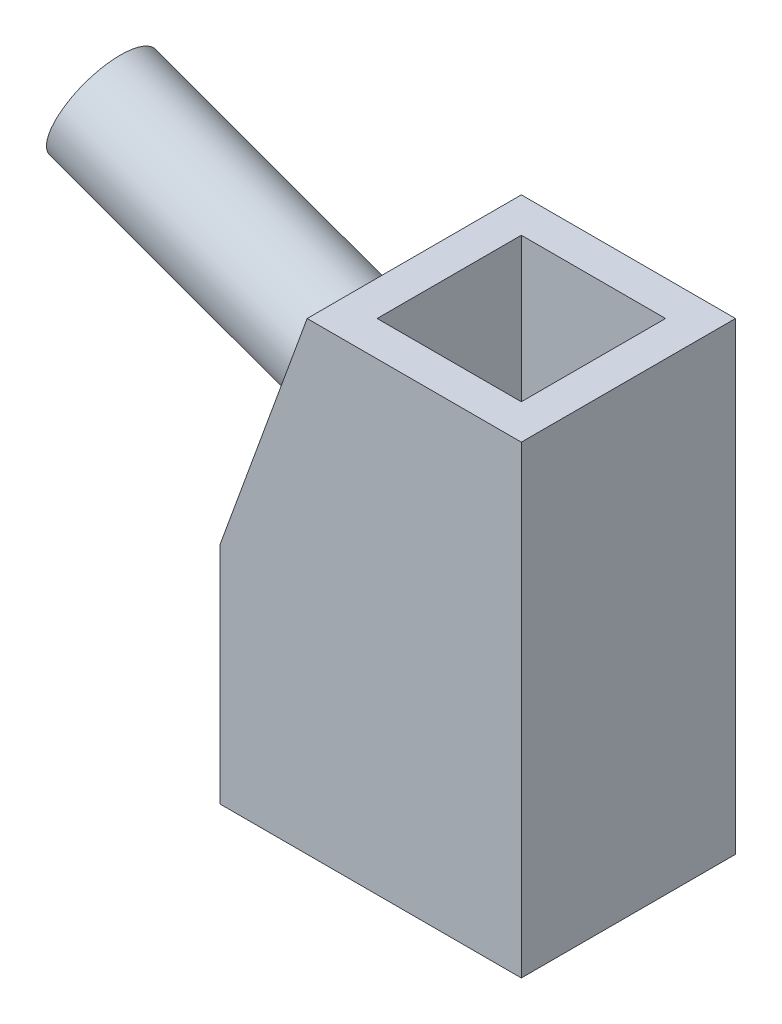
SolidWorks part; units mm, degrees
ref_plane "Front Plane" through (0, 0, 0) normal (0, 0, 1) x (1, 0, 0)
ref_plane "Top Plane" through (0, 0, 0) normal (0, 1, 0) x (1, 0, 0)
ref_plane "Right Plane" through (0, 0, 0) normal (1, 0, 0) x (0, 0, -1)
sketch "Sketch1" plane through (0, 0, 0) normal (0, 1, 0) x (1, 0, 0)
  line L1 (0, 0) -> (53.594, 0)
  line L2 (0, 0) -> (0, 38.1)
  line L3 (0, 38.1) -> (53.594, 38.1)
  line L4 (53.594, 0) -> (53.594, 38.1)
  dimension "D1" = 53.594
  dimension "D2" = 38.1
extrude "Boss-Extrude1" add sketch "Sketch1" along normal blind 82.55
sketch "Sketch4" plane through (0, 0, 0) normal (0, 0, 1) x (1, 0, 0)
  line L0 (53.594, 82.55) -> (15.494, 82.55)
  line L1 (0, 82.55) -> (53.594, 82.55) construction
  line L2 (15.494, 82.55) -> (-13.2573, 3.5565)
  line L3 (0, 82.55) -> (0, 39.9806)
  line L4 (0, 82.55) -> (0, 0) construction
  line L5 (15.494, 82.55) -> (0, 82.55)
  line M5 (53.594, 82.55) -> (0, 82.55)
  line M6 (0, 82.55) -> (0, 0)
  dimension "D1" = 38.1
  dimension "D2" = 110
extrude "Cut-Extrude1" cut sketch "Sketch4" against normal through all contours L2 M5 M6 region at (5.1647, 68.3602, 0)
sketch "Sketch5" plane through (0, 82.55, 0) normal (0, 1, 0) x (1, 0, 0)
  line L7 (15.494, 0) -> (53.594, 0) construction
  line L8 (53.594, 0) -> (53.594, 38.1) construction
  line L10 (47.371, 31.877) -> (21.717, 31.877)
  line L11 (47.371, 31.877) -> (47.371, 6.223)
  line L12 (47.371, 6.223) -> (21.717, 6.223)
  line L13 (21.717, 31.877) -> (21.717, 6.223)
  line L14 (47.371, 31.877) -> (21.717, 6.223) construction
  line L15 (47.371, 6.223) -> (21.717, 31.877) construction
  point P0 (34.544, 19.05)
  point P5 (34.544, 19.05)
  dimension "D1" = 19.05
  dimension "D2" = 19.05
  dimension "D3" = 25.654
extrude "Cut-Extrude2" cut sketch "Sketch5" against normal through all
sketch "Sketch6" plane through (-12.8495, 4.6768, 0) normal (-0.9397, 0.342, 0) x (0, 0, 1)
  line L3 (-38.1, 82.8709) -> (-38.1, 37.5695)
  line L4 (-38.1, 37.5695) -> (0, 37.5695)
  circle A0 centre (-19.05, 60.2202) radius 9.4107
  point P2 (-38.1, 60.2202)
  point P3 (-19.05, 37.5695)
  dimension "D2" = 18.8214
extrude "Boss-Extrude2" add sketch "Sketch6" along normal blind 50.8 contours A0 region at (7.747, 61.2653, -19.05)
ref_axis "Axis1" through (-34.4053, 76.6075, -19.05) along (0.9397, -0.342, 0)
equation "\"D2@Sketch6\"=0.751 - 0.01"
